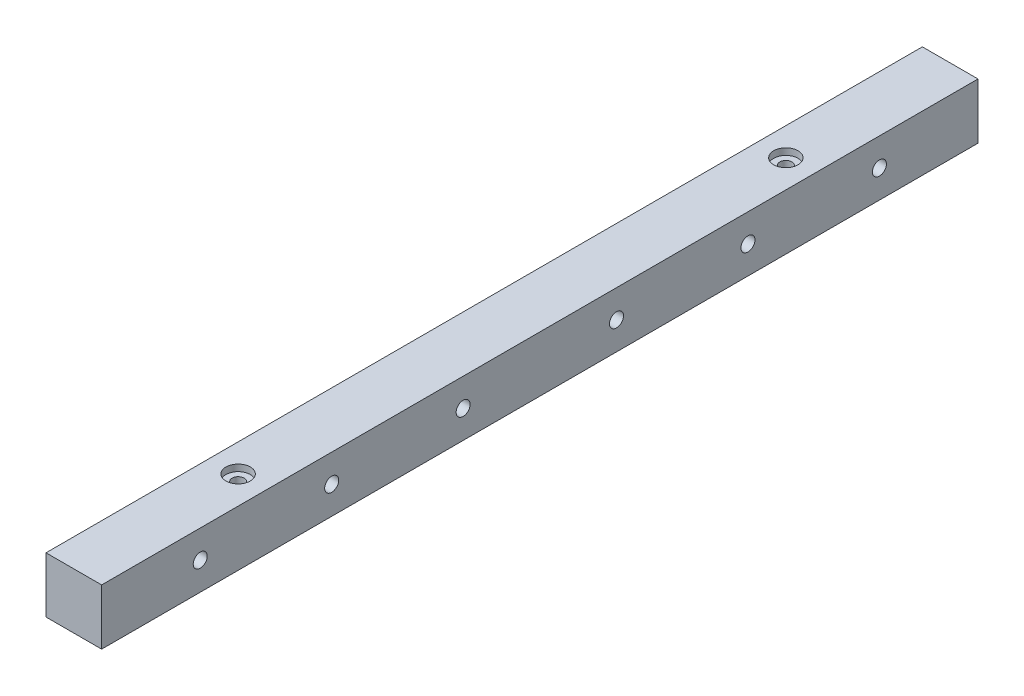
SolidWorks part; units mm, degrees
material "Delrin 2700 NC010, Low Viscosity Acetal Copolymer (SS)"
ref_plane "Front Plane" through (0, 0, 0) normal (0, 0, 1) x (1, 0, 0)
ref_plane "Top Plane" through (0, 0, 0) normal (0, 1, 0) x (1, 0, 0)
ref_plane "Right Plane" through (0, 0, 0) normal (1, 0, 0) x (0, 0, -1)
sketch "Sketch1" plane through (0, 0, 0) normal (0, 0, 1) x (1, 0, 0)
  line L0 (0, 0) -> (0, 25.6877) construction
  line L1 (12.7, -12.7) -> (-12.7, -12.7)
  line L2 (12.7, -12.7) -> (12.7, 12.7)
  line L3 (12.7, 12.7) -> (-12.7, 12.7)
  line L4 (-12.7, -12.7) -> (-12.7, 12.7)
  line L5 (0, 0) -> (36.1991, 0) construction
  dimension "D1" = 25.4
  dimension "D2" = 25.4
extrude "Boss-Extrude1" add sketch "Sketch1" along normal blind 200 and the other way blind 200
sketch "Sketch4" plane through (0, 0, 0) normal (1, 0, 0) x (0, 0, -1)
  line L0 (0, 0) -> (0, 23.5107) construction
  line L1 (-125, 23.5107) -> (-125, -37.5316) construction
  line L2 (-125, 23.5107) -> (0, 23.5107) construction
  line L3 (-125, -12.7) -> (-131, -12.7)
  line L4 (-131, -12.7) -> (-131, 2.3)
  line L5 (-131, 2.3) -> (-127.75, 4.1764)
  line L6 (-127.75, 4.1764) -> (-127.75, 9.7)
  line L7 (-127.75, 9.7) -> (-130.5563, 9.7)
  line L8 (-130.5563, 9.7) -> (-130.5563, 12.7)
  line L9 (-130.5563, 12.7) -> (-125, 12.7)
  line L10 (-125, 12.7) -> (-125, -12.7)
  line L11 (200, 12.7) -> (-200, 12.7) construction
  line L12 (200, -12.7) -> (-200, -12.7) construction
  dimension "D1" = 12
  dimension "D2" = 15
  dimension "D3" = 3
  dimension "D4" = 11.1125
  dimension "D5" = 5.5
  dimension "D6" = 60
  dimension "D7" = 250
revolve "Cut-Revolve1" cut sketch "Sketch4" angle 360 about L1
mirror "Mirror1" about plane through (0, 0, 0) normal (0, 0, 1) of "Cut-Revolve1"
sketch "Sketch5" plane through (12.7, 0, 0) normal (1, 0, 0) x (0, 0, -1)
  circle A0 centre (-155, 0) radius 3.2
  circle A1 centre (-95, 0) radius 3.2
  circle A2 centre (-35, 0) radius 3.2
  circle A3 centre (35, 0) radius 3.2
  circle A4 centre (95, 0) radius 3.2
  circle A5 centre (155, 0) radius 3.2
  circle A6 centre (155, 0) radius 3.2 construction
  circle A7 centre (95, 0) radius 3.2 construction
  circle A8 centre (35, 0) radius 3.2 construction
  circle A9 centre (-35, 0) radius 3.2 construction
  circle A10 centre (-95, 0) radius 3.2 construction
  circle A11 centre (-155, 0) radius 3.2 construction
extrude "Cut-Extrude1" cut sketch "Sketch5" against normal through all
sketch "Sketch6" plane through (-12.7, 0, 0) normal (-1, 0, 0) x (0, 0, 1)
  circle A0 centre (-155, 0) radius 4
  circle A1 centre (-95, 0) radius 4
  circle A2 centre (-35, 0) radius 4
  circle A3 centre (35, 0) radius 4
  circle A4 centre (95, 0) radius 4
  circle A5 centre (155, 0) radius 4
  circle A6 centre (-155, 0) radius 3.2 construction
  circle A7 centre (-95, 0) radius 3.2 construction
  circle A8 centre (-35, 0) radius 3.2 construction
  circle A9 centre (35, 0) radius 3.2 construction
  circle A10 centre (95, 0) radius 3.2 construction
  circle A11 centre (155, 0) radius 3.2 construction
  dimension "D1" = 8
extrude "Cut-Extrude2" cut sketch "Sketch6" against normal blind 3
ref_axis "Axis1" through (0, -12.7, -125) along (0, 1, 0)
ref_axis "Axis2" through (0, -12.7, 125) along (0, 1, 0)
